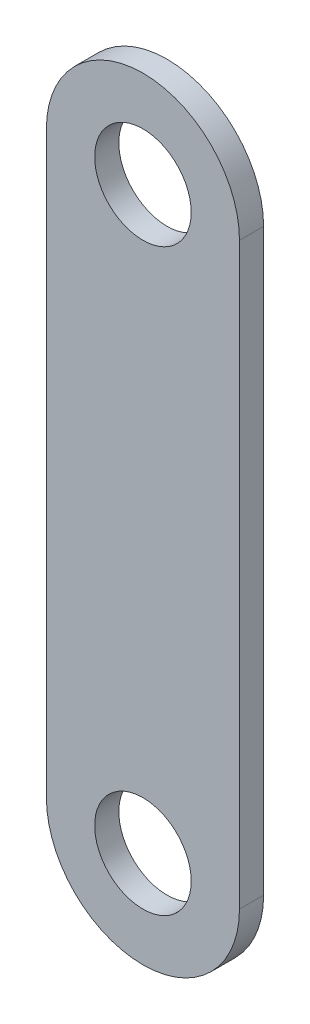
SolidWorks part; units mm, degrees
ref_plane "Front" through (0, 0, 0) normal (0, 0, 1) x (1, 0, 0)
ref_plane "Top" through (0, 0, 0) normal (0, 1, 0) x (1, 0, 0)
ref_plane "Right" through (0, 0, 0) normal (1, 0, 0) x (0, 0, -1)
sketch "Sketch1" plane through (0, 0, 0) normal (0, 0, 1) x (1, 0, 0)
  line L1 (-23.7341, 33.1296) -> (1.6659, 33.1296)
  line L2 (-23.7341, 33.1296) -> (-23.7341, -43.0704)
  line L3 (-23.7341, -43.0704) -> (1.6659, -43.0704)
  line L4 (1.6659, 33.1296) -> (1.6659, -43.0704)
  circle A0 centre (-11.0341, 33.1296) radius 12.7
  circle A1 centre (-11.0341, -43.0704) radius 12.7
  circle A2 centre (-11.0341, 33.1296) radius 6.35
  circle A3 centre (-11.0341, -43.0704) radius 6.35
  dimension "D1" = 12.7
  dimension "D2" = 12.7
  dimension "D3" = 25.4
  dimension "D5" = 25.4
  dimension "D4" = 25.4
  dimension "D6" = 76.2
extrude "Boss-Extrude1" add sketch "Sketch1" along normal blind 3.175 contours A1 L4 A0 L2 | A2 L1 A0 | A2 L1 A0 | A3 L3 A1 | A3 L3 A1 | A1 A0 L2 region at (-11.0341, 39.7636, 0) region at (-1.5091, 32.8456, 0) region at (-11.0341, -4.9704, 0) region at (-11.0341, -55.4864, 0) region at (-1.5091, -42.7864, 0)
